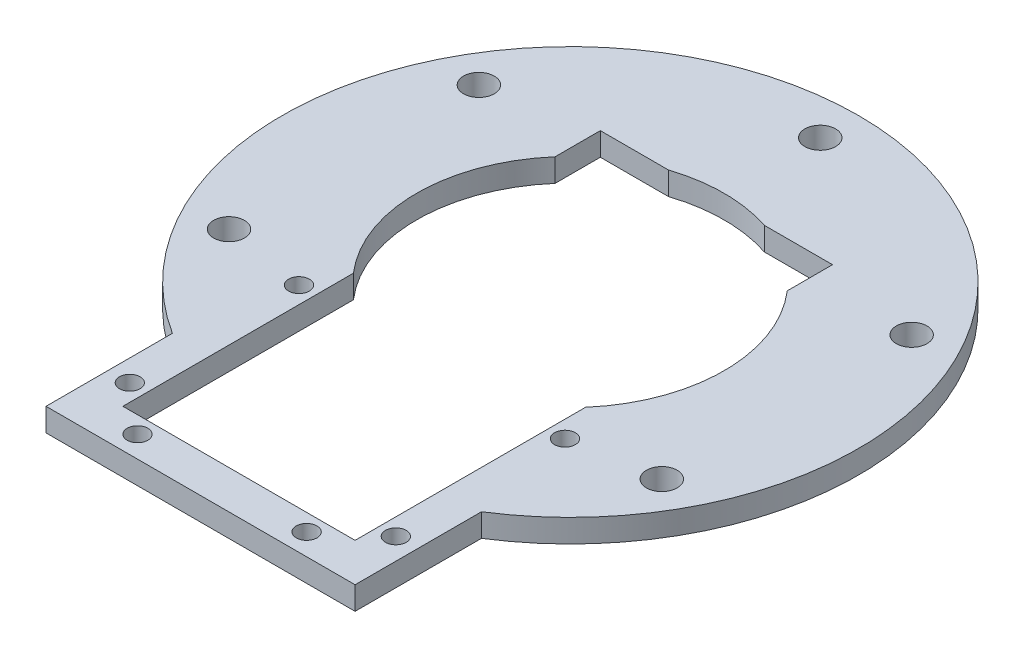
SolidWorks part; units mm, degrees
material "Acrylic (Medium-high impact)"
ref_plane "Front Plane" through (0, 0, 0) normal (0, 0, 1) x (1, 0, 0)
ref_plane "Top Plane" through (0, 0, 0) normal (0, 1, 0) x (1, 0, 0)
ref_plane "Right Plane" through (0, 0, 0) normal (1, 0, 0) x (0, 0, -1)
sketch "Sketch1" plane through (0, 0, 0) normal (0, 1, 0) x (1, 0, 0)
  circle A0 centre (0, 0) radius 37.5
  circle A1 centre (0, 0) radius 32.5 construction
  circle A2 centre (0, 32.5) radius 2
  circle A3 centre (28.1458, 16.25) radius 2
  circle A4 centre (28.1458, -16.25) radius 2
  circle A5 centre (0, -32.5) radius 2
  circle A6 centre (-28.1458, -16.25) radius 2
  circle A7 centre (-28.1458, 16.25) radius 2
  point P18 (0, 0)
  dimension "D1" = 75
  dimension "D2" = 65
  dimension "D3" = 4
  dimension "D4" = 6
extrude "Boss-Extrude1" add sketch "Sketch1" along normal blind 3
sketch "Sketch2" plane through (0, 3, 0) normal (0, 1, 0) x (1, 0, 0)
  line L0 (-20.1, 19) -> (-20.1, -48.1)
  line L1 (-20.1, -48.1) -> (20.1, -48.1)
  line L2 (20.1, -48.1) -> (20.1, 19)
  line L3 (-15.1, 19) -> (-15.1, -43.1)
  line L4 (-15.1, -43.1) -> (15.1, -43.1)
  line L5 (15.1, -43.1) -> (15.1, 19)
  line L6 (20.1, 19) -> (15.1, 19)
  line L7 (-20.1, 19) -> (-15.1, 19)
  line L8 (20.1, 13) -> (-20.1, 13) construction
  line L9 (15.1, 19) -> (-15.1, 19)
  circle A0 centre (17.3, 4) radius 1.35
  circle A1 centre (17.3, -18) radius 1.35
  circle A2 centre (17.3, -40) radius 1.35
  circle A3 centre (-17.3, 4) radius 1.35
  circle A4 centre (-17.3, -18) radius 1.35
  circle A5 centre (-17.3, -40) radius 1.35
  circle A6 centre (-11, -45.3) radius 1.35
  circle A7 centre (11, -45.3) radius 1.35
  circle A8 centre (0, 0) radius 14 construction
  point P14 (0, 13)
  point P15 (0, -43.1)
  circle M13 centre (0, 0) radius 37.5
  circle M15 centre (0, -32.5) radius 2
  dimension "D1" = 2.7
  dimension "D2" = 28
  dimension "D3" = 4
  dimension "D4" = 22
  dimension "D5" = 22
  dimension "D6" = 45.3
  dimension "D7" = 40.2
  dimension "D8" = 22
  dimension "D9" = 34.6
  dimension "D10" = 11
  dimension "D11" = 17.3
  dimension "D12" = 30.2
  dimension "D13" = 61.1
  dimension "D14" = 6
  dimension "D15" = 5
  dimension "D16" = 43.1
  dimension "D17" = 13
  dimension "D18" = 5
  dimension "D19" = 43.1
extrude "Boss-Extrude2" add sketch "Sketch2" against normal through all contours L5 L4 L3 L0 L1 L2 A7 A6 A5 A2 M13 region at (0, 3, 43.1256)
extrude "Cut-Extrude1" cut sketch "Sketch2<3>" against normal through all contours L5 L9 L3 M13 M15 | A3 | A4 | A1 | A0 region at (0, 3, 8.5586) region at (-17.3, 3, -4)
sketch "Sketch2<3>" plane through (0, 3, 0) normal (0, 1, 0) x (1, 0, 0) same geometry as "Sketch2"
sketch "Sketch3" plane through (0, 3, 0) normal (0, 1, 0) x (1, 0, 0)
  circle A0 centre (0, 0) radius 20
  dimension "D1" = 40
extrude "Cut-Extrude2" cut sketch "Sketch3" against normal through all
